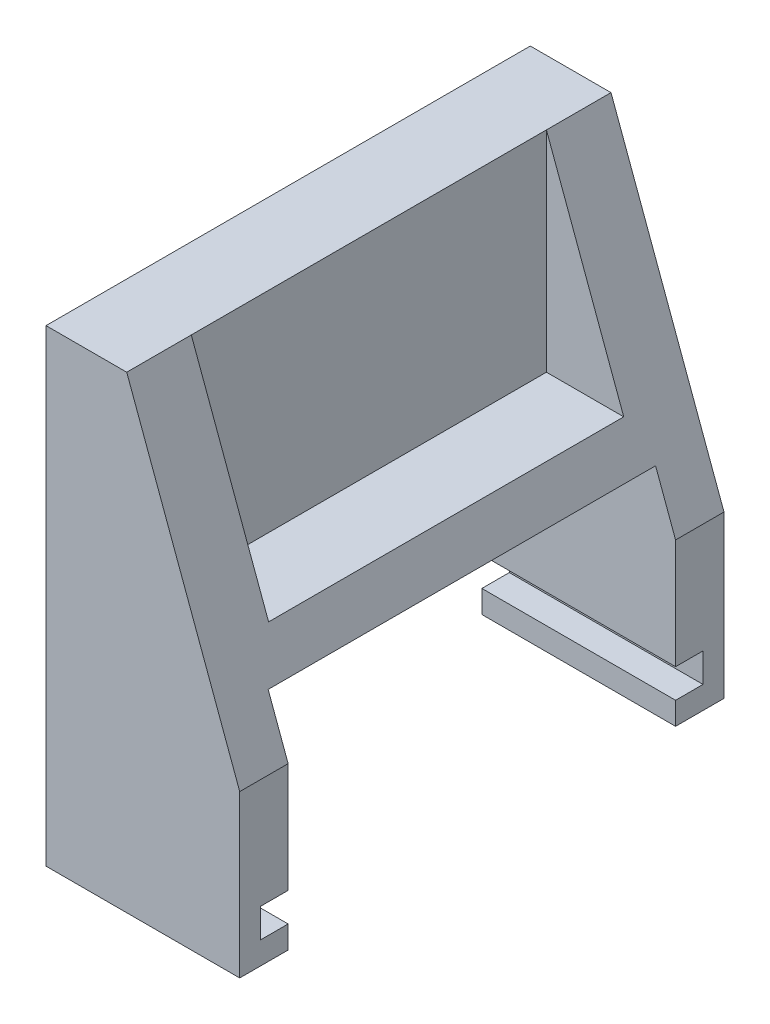
SolidWorks part; units mm, degrees
ref_plane "Front Plane" through (0, 0, 0) normal (0, 0, 1) x (1, 0, 0)
ref_plane "Top Plane" through (0, 0, 0) normal (0, 1, 0) x (1, 0, 0)
ref_plane "Right Plane" through (0, 0, 0) normal (1, 0, 0) x (0, 0, -1)
sketch "Sketch1" plane through (0, 0, 0) normal (0, 0, 1) x (1, 0, 0)
  line L0 (0, 0) -> (0, -29)
  line L1 (0, -29) -> (12, -29)
  line L2 (12, -29) -> (12, -19)
  line L3 (12, -19) -> (5, 0)
  line L4 (5, 0) -> (0, 0)
  dimension "D1" = 29
  dimension "D2" = 12
  dimension "D3" = 10
  dimension "D4" = 5
extrude "Boss-Extrude1" add sketch "Sketch1" against normal blind 30
sketch "Sketch4" plane through (0, 0, 0) normal (-1, 0, 0) x (0, 0, 1)
  line L0 (-30, 0) -> (-30, -29) construction
  line L1 (-27, -15.6386) -> (-3, -15.6386)
  line L2 (-27, -15.6386) -> (-27, -29.6386)
  line L3 (-27, -29.6386) -> (-3, -29.6386)
  line L4 (-3, -15.6386) -> (-3, -29.6386)
  point P4 (-27, -22.6386)
  dimension "D1" = 24
  dimension "D2" = 14
  dimension "D3" = 3
extrude "Cut-Extrude2" cut sketch "Sketch4" against normal blind 25 contours L2 L1 L4 L3
sketch "Sketch5" plane through (0, 0, 0) normal (-1, 0, 0) x (0, 0, 1)
  line L0 (-3, -15.6386) -> (-3, -29) construction
  line L1 (-3, -25.8) -> (-1.3, -25.8)
  line L2 (-3, -25.8) -> (-3, -27.6)
  line L3 (-3, -27.6) -> (-1.3, -27.6)
  line L4 (-1.3, -25.8) -> (-1.3, -27.6)
  line L5 (-3, -29) -> (0, -29) construction
  dimension "D1" = 1.8
  dimension "D2" = 1.7
  dimension "D3" = 1.4
extrude "Cut-Extrude3" cut sketch "Sketch5" against normal blind 15
ref_plane "Plane1" through (0, 0, -15) normal (0, 0, 1) x (1, 0, 0)
mirror "Mirror1" about plane through (0, 0, -15) normal (0, 0, 1) of "Cut-Extrude3"
sketch "Sketch6" plane through (0, 0, -15) normal (0, 0, 1) x (1, 0, 0)
  line L0 (5, 0) -> (5, -13)
  line L1 (5, -13) -> (9.7895, -13)
  line L2 (12, -19) -> (5, 0) construction
  line L3 (9.7895, -13) -> (5, 0)
  dimension "D1" = 13
extrude "Cut-Extrude4" cut sketch "Sketch6" against normal mid plane 22
ref_plane "Plane2" through (0, -15, 0) normal (0, 1, 0) x (1, 0, 0)
sketch "Sketch8" plane through (0, -15, 0) normal (0, 1, 0) x (0, 0, -1)
  line L0 (20.1377, 8.7684) -> (5.6377, 8.7684)
  line L2 (5.6377, 8.7684) -> (5.6377, 8.2684)
  line L3 (20.1377, 8.7684) -> (20.1377, 8.2684)
  line L4 (20.1377, 8.2684) -> (19.7377, 8.2684)
  line L5 (19.2566, 7.5194) -> (18.9733, 8.2684)
  line L6 (19.7377, 8.2684) -> (19.4566, 7.5194)
  line L7 (19.4566, 7.5194) -> (19.2566, 7.5194)
  line L8 (18.2566, 7.5194) -> (17.9733, 8.2684)
  line L9 (18.4566, 7.5194) -> (18.2566, 7.5194)
  line L10 (18.7377, 8.2684) -> (18.4566, 7.5194)
  line L11 (17.2566, 7.5194) -> (16.9733, 8.2684)
  line L12 (17.4566, 7.5194) -> (17.2566, 7.5194)
  line L13 (17.7377, 8.2684) -> (17.4566, 7.5194)
  line L14 (16.2566, 7.5194) -> (15.9733, 8.2684)
  line L15 (16.4566, 7.5194) -> (16.2566, 7.5194)
  line L16 (16.7377, 8.2684) -> (16.4566, 7.5194)
  line L17 (15.2566, 7.5194) -> (14.9733, 8.2684)
  line L18 (15.4566, 7.5194) -> (15.2566, 7.5194)
  line L19 (15.7377, 8.2684) -> (15.4566, 7.5194)
  line L20 (14.2566, 7.5194) -> (13.9733, 8.2684)
  line L21 (14.4566, 7.5194) -> (14.2566, 7.5194)
  line L22 (14.7377, 8.2684) -> (14.4566, 7.5194)
  line L23 (13.2566, 7.5194) -> (12.9733, 8.2684)
  line L24 (13.4566, 7.5194) -> (13.2566, 7.5194)
  line L25 (13.7377, 8.2684) -> (13.4566, 7.5194)
  line L26 (12.2566, 7.5194) -> (11.9733, 8.2684)
  line L27 (12.4566, 7.5194) -> (12.2566, 7.5194)
  line L28 (12.7377, 8.2684) -> (12.4566, 7.5194)
  line L29 (11.2566, 7.5194) -> (10.9733, 8.2684)
  line L30 (11.4566, 7.5194) -> (11.2566, 7.5194)
  line L31 (11.7377, 8.2684) -> (11.4566, 7.5194)
  line L32 (10.2566, 7.5194) -> (9.9733, 8.2684)
  line L33 (10.4566, 7.5194) -> (10.2566, 7.5194)
  line L34 (10.7377, 8.2684) -> (10.4566, 7.5194)
  line L35 (9.2566, 7.5194) -> (8.9733, 8.2684)
  line L36 (9.4566, 7.5194) -> (9.2566, 7.5194)
  line L37 (9.7377, 8.2684) -> (9.4566, 7.5194)
  line L38 (8.2566, 7.5194) -> (7.9733, 8.2684)
  line L39 (8.4566, 7.5194) -> (8.2566, 7.5194)
  line L40 (8.7377, 8.2684) -> (8.4566, 7.5194)
  line L41 (7.2566, 7.5194) -> (6.9733, 8.2684)
  line L42 (7.4566, 7.5194) -> (7.2566, 7.5194)
  line L43 (7.7377, 8.2684) -> (7.4566, 7.5194)
  line L44 (6.2566, 7.5194) -> (5.9733, 8.2684)
  line L45 (6.4566, 7.5194) -> (6.2566, 7.5194)
  line L46 (6.7377, 8.2684) -> (6.4566, 7.5194)
  line L47 (19.2566, 7.5194) -> (18.2566, 7.5194) construction
  line L48 (18.9733, 8.2684) -> (18.7377, 8.2684)
  line L49 (17.9733, 8.2684) -> (17.7377, 8.2684)
  line L50 (16.9733, 8.2684) -> (16.7377, 8.2684)
  line L51 (15.9733, 8.2684) -> (15.7377, 8.2684)
  line L52 (14.9733, 8.2684) -> (14.7377, 8.2684)
  line L53 (13.9733, 8.2684) -> (13.7377, 8.2684)
  line L54 (12.9733, 8.2684) -> (12.7377, 8.2684)
  line L55 (11.9733, 8.2684) -> (11.7377, 8.2684)
  line L56 (10.9733, 8.2684) -> (10.7377, 8.2684)
  line L57 (9.9733, 8.2684) -> (9.7377, 8.2684)
  line L58 (8.9733, 8.2684) -> (8.7377, 8.2684)
  line L59 (7.9733, 8.2684) -> (7.7377, 8.2684)
  line L60 (6.9733, 8.2684) -> (6.7377, 8.2684)
  line L61 (5.9733, 8.2684) -> (5.6377, 8.2684)
  dimension "D1" = 0.8
  dimension "D4" = 0.2
  dimension "D2" = 14.5
  dimension "D3" = 0.5
  dimension "D5" = 1
  dimension "D6" = 0.4
